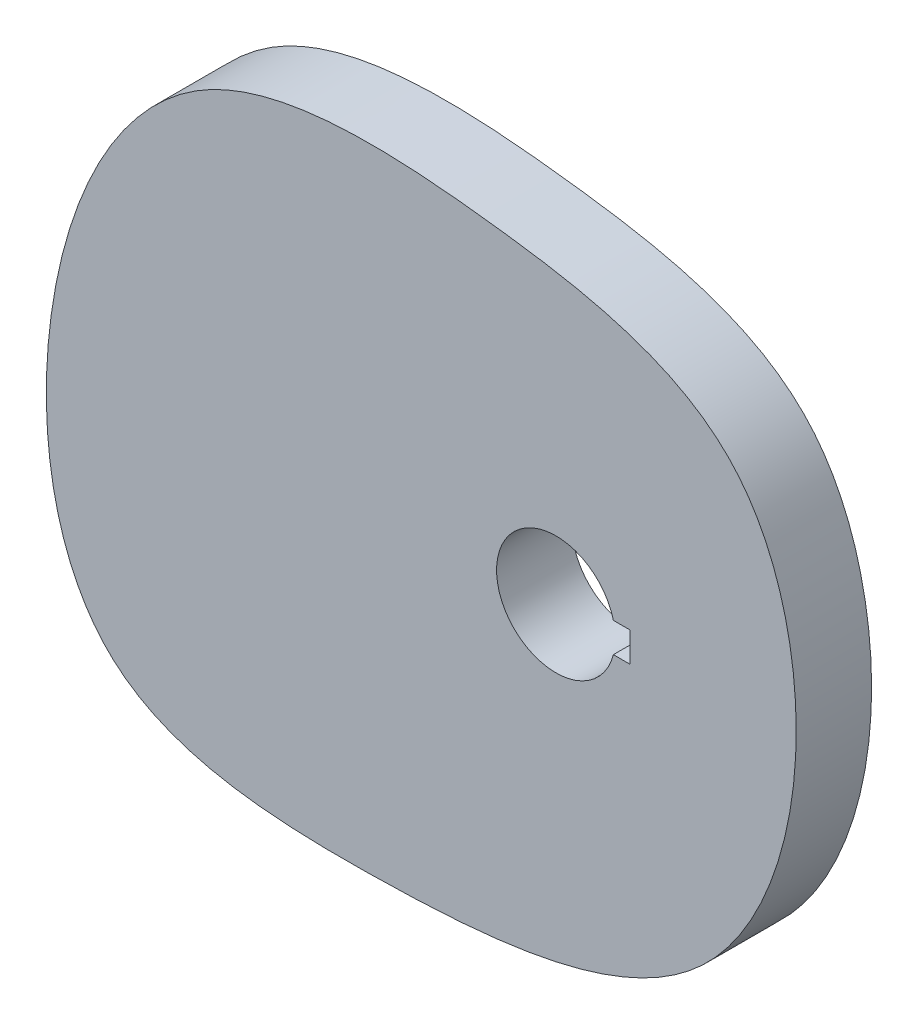
SolidWorks part; units mm, degrees
ref_plane "Front" through (0, 0, 0) normal (0, 0, 1) x (1, 0, 0)
ref_plane "Top" through (0, 0, 0) normal (0, 1, 0) x (1, 0, 0)
ref_plane "Right" through (0, 0, 0) normal (1, 0, 0) x (0, 0, -1)
other "Configuration Table"
ref_axis "Axis1" through (0, 0, -80.9) along (0, 0, 1)
sketch "Sketch1" plane through (0, 0, 0) normal (0, 0, 1) x (1, 0, 0)
  line L0 (-105.2567, 30.1594) -> (-35.9069, 67.2096) construction
  line L1 (-101.6, -67.31) -> (22.0337, -67.31) construction
  line L2 (19.3649, 5) -> (25, 5)
  line L4 (19.3649, -5) -> (25, -5)
  line L5 (25, 5) -> (25, -5)
  arc A0 (22.0337, -67.31) -> (52.8808, -54.864) centre (22.0337, -22.86) ccw construction
  arc A1 (-141.0169, -11.1608) -> (-101.6, -67.31) centre (-101.6, -25.4) ccw construction
  arc A2 (-105.2567, 30.1594) -> (-141.0169, -11.1608) centre (-69.3498, -37.0503) ccw construction
  arc A3 (-26.9632, 71.2701) -> (52.8808, -54.864) centre (0, 0) cw construction
  arc A4 (19.3649, 5) -> (19.3649, -5) centre (0, 0) ccw
  arc A5 (-35.9069, 67.2096) -> (-26.9632, 71.2701) centre (0, 0) cw construction
  spline S0 degree 3 poles (62.0064, -101.041) (89.9578, 3.7101) (61.3817, 86.2907) (-25.3122, 103.2071) (-130.7316, 107.8056) (-180.0436, 6.7014) (-165.3427, -107.5476) (-50.7565, -112.6019) (62.0064, -101.041) (89.9578, 3.7101) (61.3817, 86.2907) knots -0.416622 -0.292963 -0.140033 0 0.07223 0.186829 0.321625 0.459718 0.583378 0.707037 0.859967 1 1.07223 1.186829 1.321625 only from (80, 20) to (80, 20)
  point P5 (25, 0)
  dimension "D1" = 44.45
  dimension "D3" = 76.2
  dimension "D4" = 76.2
  dimension "D5" = 41.91
  dimension "D7" = 40
  dimension "D2" = 101.6
  dimension "D6" = 25.4
  dimension "D8" = 25
  dimension "D9" = 10
extrude "Extrude1" add sketch "Sketch1" along normal mid plane 25.4
